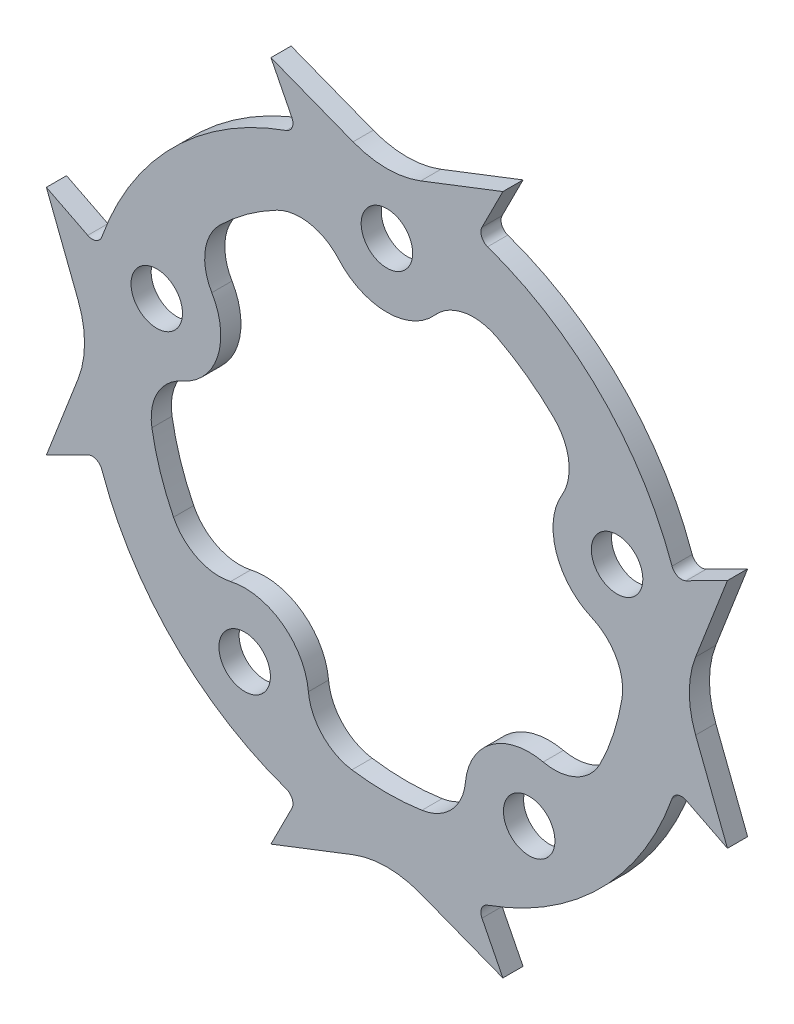
SolidWorks part; units mm, degrees
ref_plane "Front Plane" through (0, 0, 0) normal (0, 0, 1) x (1, 0, 0)
ref_plane "Top Plane" through (0, 0, 0) normal (0, 1, 0) x (1, 0, 0)
ref_plane "Right Plane" through (0, 0, 0) normal (1, 0, 0) x (0, 0, -1)
sketch "Sketch1" plane through (0, 0, 0) normal (0, 0, 1) x (1, 0, 0)
  line L0 (0, 24) -> (0, 0) construction
  line L1 (0, -23.6347) -> (0, -29.9847) construction
  line L2 (0, 0) -> (-11.5, 33.7706) construction
  line L3 (-11.5, 33.7706) -> (-8.9038, 28.6322)
  line L4 (-11.5, 33.7706) -> (-3.3557, 30.6125)
  line L5 (-11.5, 33.7706) -> (-3.7663, 36.4042) construction
  line L6 (0, 0) -> (0, 35.675) construction
  line L7 (11.5, 33.7706) -> (3.3557, 30.6125)
  line L8 (11.5, 33.7706) -> (8.9038, 28.6322)
  line L9 (-9.6657, 28.3841) -> (47321.284, 16146.1136) construction
  circle A0 centre (0, 0) radius 29.9847
  circle A1 centre (0, 24) radius 2.5527
  arc A2 (4.7678, 19.8059) -> (-4.7678, 19.8059) centre (0, 24) cw
  arc A3 (-23.3071, -3.9214) -> (-21.1608, -10.5271) centre (0, 0) ccw
  arc A4 (4.7678, 19.8059) -> (10.9318, 20.9546) centre (8.5821, 16.4507) cw
  arc A5 (-4.7678, 19.8059) -> (-10.9318, 20.9546) centre (-8.5821, 16.4507) ccw
  arc A6 (20.3099, 1.5859) -> (17.3632, 10.6548) centre (22.8254, 7.4164) cw
  circle A7 centre (22.8254, 7.4164) radius 2.5527
  arc A8 (17.3632, 10.6548) -> (16.5509, 16.872) centre (12.9935, 13.2456) ccw
  arc A9 (20.3099, 1.5859) -> (23.3071, -3.9214) centre (18.2975, -3.0785) cw
  arc A10 (7.7844, -18.8258) -> (15.4989, -13.2209) centre (14.1068, -19.4164) cw
  circle A11 centre (14.1068, -19.4164) radius 2.5527
  arc A12 (15.4989, -13.2209) -> (21.1608, -10.5271) centre (16.6125, -8.2644) ccw
  arc A13 (7.7844, -18.8258) -> (3.4728, -23.3782) centre (2.7264, -18.3533) cw
  arc A14 (-15.4989, -13.2209) -> (-7.7844, -18.8258) centre (-14.1068, -19.4164) cw
  circle A15 centre (-14.1068, -19.4164) radius 2.5527
  arc A16 (-7.7844, -18.8258) -> (-3.4728, -23.3782) centre (-2.7264, -18.3533) ccw
  arc A17 (-15.4989, -13.2209) -> (-21.1608, -10.5271) centre (-16.6125, -8.2644) cw
  arc A18 (-17.3632, 10.6548) -> (-20.3099, 1.5859) centre (-22.8254, 7.4164) cw
  circle A19 centre (-22.8254, 7.4164) radius 2.5527
  arc A20 (-20.3099, 1.5859) -> (-23.3071, -3.9214) centre (-18.2975, -3.0785) ccw
  arc A21 (-17.3632, 10.6548) -> (-16.5509, 16.872) centre (-12.9935, 13.2456) cw
  arc A22 (-3.4728, -23.3782) -> (3.4728, -23.3782) centre (0, 0) ccw
  arc A23 (21.1608, -10.5271) -> (23.3071, -3.9214) centre (0, 0) ccw
  arc A24 (16.5509, 16.872) -> (10.9318, 20.9546) centre (0, 0) ccw
  arc A25 (-10.9318, 20.9546) -> (-16.5509, 16.872) centre (0, 0) ccw
  circle A26 centre (0, 0) radius 35.675 construction
  arc A27 (-3.3557, 30.6125) -> (0, 29.9847) centre (0, 39.2664) ccw
  arc A29 (3.3557, 30.6125) -> (0, 29.9847) centre (0, 39.2664) cw
  point P53 (-49.7465, 12.6804)
  point P54 (-25.8696, -2.3039)
  point P55 (-45.1984, 27.8403)
  dimension "D2" = 5.1054
  dimension "D4" = 5.08
  dimension "D5" = 6.35
  dimension "D6" = 24
  dimension "D3" = 6.35
  dimension "D8" = 71.35
  dimension "D12" = 59.9694
  dimension "D9" = 8
  dimension "D10" = 40
  dimension "D11" = 23
  dimension "D7" = 5
extrude "Boss-Extrude1" add sketch "Sketch1" along normal blind 2 contours A0 A25 A5 A2 A4 A24 A8 A6 A9 A23 A12 A10 A13 A22 A16 A14 A17 A3 A20 A18 A21 A19 A15 A11 A7 A1 region at (-4.3756, 28.8062, 0)
extrude "Boss-Extrude2" add sketch "Sketch1<4>" along normal up to surface (2 mm away) contours A27 L4 L3 A0 | L7 A29 A0 L8 region at (-7.4005, 30.8552, 0) region at (7.4005, 30.8552, 0) up to face at (0, 0, 2)
sketch "Sketch1<4>" plane through (0, 0, 0) normal (0, 0, 1) x (1, 0, 0) same geometry as "Sketch1"
fillet "Fillet1" radius 1 2 edges at (8.9038, 28.6322, 1) (-8.9038, 28.6322, 1)
pattern_circular "CirPattern1" count 4 over 360 about axis through (0, 0, 2) along (0, 0, 1) of "Fillet1", "Boss-Extrude2"
